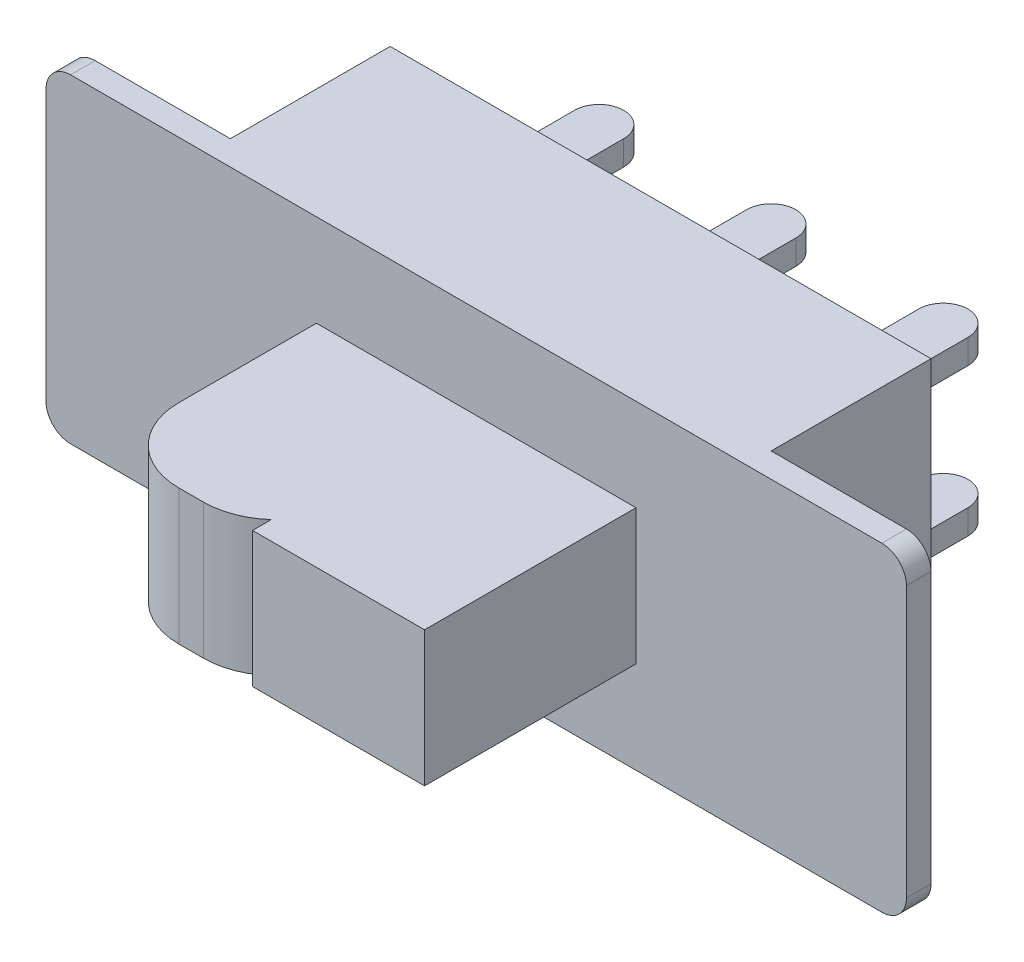
SolidWorks part; units mm, degrees
ref_plane "Спереди" through (0, 0, 0) normal (0, 0, 1) x (1, 0, 0)
ref_plane "Сверху" through (0, 0, 0) normal (0, 1, 0) x (1, 0, 0)
ref_plane "Справа" through (0, 0, 0) normal (1, 0, 0) x (0, 0, -1)
sketch "Эскиз1" plane through (0, 0, 0) normal (0, 0, 1) x (1, 0, 0)
  line L1 (0, 0) -> (22, 0)
  line L2 (0, 0) -> (0, 13)
  line L3 (0, 13) -> (22, 13)
  line L4 (22, 0) -> (22, 13)
  dimension "D1" = 22
  dimension "D2" = 13
extrude "Бобышка-Вытянуть1" add sketch "Эскиз1" along normal blind 7.5
sketch "Эскиз2" plane through (0, 0, 7.5) normal (0, 0, 1) x (1, 0, 0)
  line L0 (-6.5, 14.8946) -> (-6.5, -3.2277) construction
  line L1 (28.5, 14.8946) -> (28.5, -3.2277) construction
  line L2 (11, 13) -> (11, 0) construction
  line L3 (22, 13) -> (0, 13) construction
  line L4 (0, 0) -> (22, 0) construction
  line L6 (0, 0) -> (-6.5, 0)
  line L7 (0, 0) -> (0, 13)
  line L8 (0, 13) -> (-6.5, 13)
  line L9 (-6.5, 0) -> (-6.5, 13)
  line L10 (22, 13) -> (28.5, 13)
  line L11 (22, 13) -> (22, 0)
  line L12 (22, 0) -> (28.5, 0)
  line L13 (28.5, 13) -> (28.5, 0)
  dimension "D1" = 17.5
  dimension "D2" = 17.5
extrude "Бобышка-Вытянуть2" add sketch "Эскиз2" against normal blind 1
fillet "Скругление1" radius 1 4 edges at (28.5, 13, 7) (28.5, 0, 7) (-6.5, 13, 7) (-6.5, 0, 7)
ref_plane "Плоскость1" through (0, 3.5, 0) normal (0, -1, 0) x (-1, 0, 0)
sketch "Эскиз3" plane through (0, 3.5, 0) normal (0, -1, 0) x (-1, 0, 0)
  line L0 (0, 0) -> (-22, 0) construction
  line L1 (-3, 0) -> (-5, 0)
  line L2 (-3, 0) -> (-3, 5.5)
  line L3 (-3, 5.5) -> (-5, 5.5)
  line L4 (-5, 0) -> (-5, 5.5)
  line L6 (-17, 0) -> (-19, 0)
  line L7 (-17, 0) -> (-17, 5.5)
  line L8 (-17, 5.5) -> (-19, 5.5)
  line L9 (-19, 0) -> (-19, 5.5)
  line L10 (-10, 0) -> (-12, 0)
  line L11 (-10, 0) -> (-10, 5.5)
  line L12 (-10, 5.5) -> (-12, 5.5)
  line L13 (-12, 0) -> (-12, 5.5)
  point P14 (-11, 0)
  point P15 (-11, 0)
  point P16 (-4, 0)
  point P17 (-18, 0)
  dimension "D1" = 7
  dimension "D2" = 7
  dimension "D3" = 2
  dimension "D4" = 2
  dimension "D5" = 2
  dimension "D6" = 5.5
extrude "Бобышка-Вытянуть3" add sketch "Эскиз3" along normal blind 0.5 and the other way blind 0.5
fillet "Скругление2" radius 1 6 edges at (19, 3.5, -5.5) (17, 3.5, -5.5) (12, 3.5, -5.5) (10, 3.5, -5.5) (5, 3.5, -5.5) (3, 3.5, -5.5)
ref_plane "Плоскость2" through (0, 6.5, 0) normal (0, -1, 0) x (-1, 0, 0)
mirror "Зеркальное отражение1" about plane through (0, 6.5, 0) normal (0, -1, 0) of "Скругление2", "Бобышка-Вытянуть3"
sketch "Эскиз4" plane through (0, 0, 7.5) normal (0, 0, 1) x (1, 0, 0)
  line L0 (-6.5, 6.5) -> (28.5, 6.5) construction
  line L1 (-6.5, 12) -> (-6.5, 1) construction
  line L2 (28.5, 1) -> (28.5, 12) construction
  line L4 (4.5, 9.25) -> (11.5, 9.25)
  line L5 (4.5, 9.25) -> (4.5, 3.75)
  line L6 (4.5, 3.75) -> (11.5, 3.75)
  line L7 (11.5, 9.25) -> (11.5, 3.75)
  line L8 (4.5, 9.25) -> (11.5, 3.75) construction
  line L9 (4.5, 3.75) -> (11.5, 9.25) construction
  point P6 (8, 6.5)
  point P11 (11, 6.5)
  dimension "D1" = 7
  dimension "D2" = 5.5
  dimension "D3" = 3
extrude "Бобышка-Вытянуть4" add sketch "Эскиз4" along normal blind 8.6
fillet "Скругление3" radius 3 2 edges at (4.5, 6.5, 16.1) (11.5, 6.5, 16.1)
ref_plane "Плоскость3" through (11, 0, 0) normal (1, 0, 0) x (0, 0, -1)
mirror "Зеркальное отражение4" about plane through (11, 0, 0) normal (1, 0, 0) of "Бобышка-Вытянуть4"
